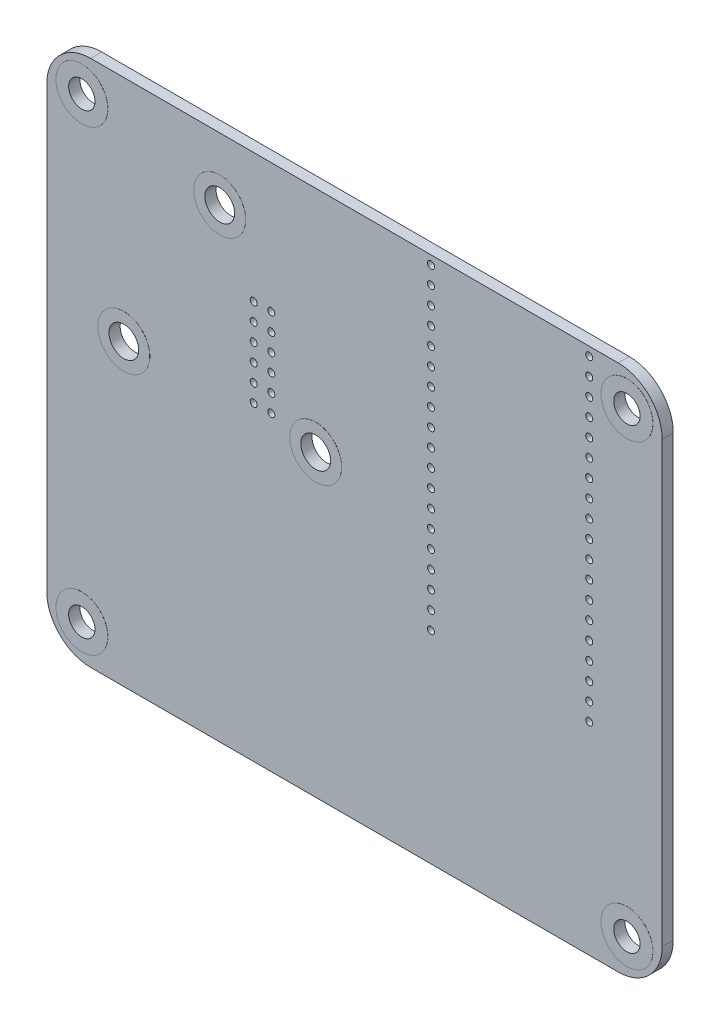
SolidWorks part; units mm, degrees
ref_plane "Front Plane" through (0, 0, 0) normal (0, 0, 1) x (1, 0, 0)
ref_plane "Top Plane" through (0, 0, 0) normal (0, 1, 0) x (1, 0, 0)
ref_plane "Right Plane" through (0, 0, 0) normal (1, 0, 0) x (0, 0, -1)
sketch "Sketch1" plane through (0, 0, 0) normal (0, 0, 1) x (1, 0, 0)
  line L1 (0, -76.2) -> (88.9, -76.2)
  line L2 (0, -76.2) -> (0, 0)
  line L3 (0, 0) -> (88.9, 0)
  line L4 (88.9, -76.2) -> (88.9, 0)
  point P4 (0, 0)
  point P5 (0, 0)
  dimension "D1" = 76.2
  dimension "D2" = 88.9
extrude "Boss-Extrude1" add sketch "Sketch1" along normal blind 1.6
sketch "Sketch2" plane through (0, 0, 0) normal (0, 0, -1) x (-1, 0, 0)
  circle A8 centre (-38.8564, -33) radius 2.15 construction
  circle A9 centre (-11.1436, -33) radius 2.15 construction
  circle A10 centre (-25, -9) radius 2.15 construction
  circle A11 centre (-38.8564, -33) radius 2.15
  circle A12 centre (-11.1436, -33) radius 2.15
  circle A13 centre (-25, -9) radius 2.15
extrude "Cut-Extrude1" cut sketch "Sketch2" against normal through all
sketch "Sketch4" plane through (0, 0, 0) normal (0, 0, -1) x (-1, 0, 0)
  line L0 (-44.45, 0) -> (-44.45, -76.2) construction
  line L1 (-88.9, 0) -> (0, 0) construction
  line L2 (0, -76.2) -> (-88.9, -76.2) construction
  line L3 (-88.9, -38.1) -> (0, -38.1) construction
  line L4 (-88.9, -76.2) -> (-88.9, 0) construction
  line L5 (0, 0) -> (0, -76.2) construction
  circle A0 centre (-5.08, -5.08) radius 1.905
  circle A1 centre (-83.82, -5.08) radius 1.905
  circle A2 centre (-83.82, -71.12) radius 1.905
  circle A3 centre (-5.08, -71.12) radius 1.905
  dimension "D1" = 3.81
  dimension "D2" = 5.08
  dimension "D3" = 5.08
extrude "Cut-Extrude2" cut sketch "Sketch4" against normal through all
fillet "Fillet1" radius 6.35 4 edges at (88.9, 0, 0.8) (88.9, -76.2, 0.8) (0, -76.2, 0.8) (0, 0, 0.8)
ref_plane "Plane1" through (44.45, 0, 0) normal (-1, 0, 0) x (0, 0, 1)
sketch "Sketch6" plane through (0, 0, 0) normal (0, 0, -1) x (-1, 0, 0)
  circle A0 centre (-5.08, -71.12) radius 3.75
  circle A1 centre (-5.08, -5.08) radius 3.75
  circle A2 centre (-11.1436, -33) radius 3.75
  circle A3 centre (-38.8564, -33) radius 3.75
  circle A4 centre (-25, -9) radius 3.75
  circle A5 centre (-83.82, -5.08) radius 3.75
  circle A6 centre (-83.82, -71.12) radius 3.75
  point P20 (-5.08, -71.12)
  circle M3 centre (-5.08, -71.12) radius 1.905
  circle M4 centre (-83.82, -71.12) radius 1.905
  circle M5 centre (-83.82, -5.08) radius 1.905
  circle M6 centre (-5.08, -5.08) radius 1.905
  circle M7 centre (-38.8564, -33) radius 2.15
  circle M8 centre (-11.1436, -33) radius 2.15
  circle M9 centre (-25, -9) radius 2.15
  dimension "D1" = 7.5
extrude "Boss-Extrude2" add sketch "Sketch6" along normal blind 0.01 contours A1 M6 | A4 M9 | A2 M8 | A0 M3 | A3 M7 | A5 M5 | A6 M4 region at (8.7239, -71.12, 0) region at (8.7239, -5.08, 0) region at (14.7875, -33, 0) region at (42.5003, -33, 0) region at (28.6439, -9, 0) region at (87.4639, -5.08, 0) region at (87.4639, -71.12, 0)
ref_plane "Plane2" through (0, 0, 0.8) normal (0, 0, 1) x (1, 0, 0)
mirror "Mirror1" about plane through (0, 0, 0.8) normal (0, 0, 1) of "Boss-Extrude2"
sketch "Sketch7" plane through (0, 0, 1.6) normal (0, 0, 1) x (1, 0, 0)
  line L4 (78.5658, -1.0536) -> (78.1658, -1.0536)
  line L5 (78.5658, -1.4536) -> (78.5658, -1.0536)
  line L6 (78.1658, -1.4536) -> (78.5658, -1.4536)
  line L7 (78.1658, -1.0536) -> (78.1658, -1.4536)
  line L8 (78.5658, -1.0536) -> (78.1658, -1.0536)
  line L11 (78.1658, -1.0536) -> (78.1658, -1.4536)
  circle A0 centre (29.897, -31.35) radius 0.508
  circle A1 centre (32.437, -31.35) radius 0.508
  circle A2 centre (32.437, -28.81) radius 0.508
  circle A3 centre (32.437, -26.27) radius 0.508
  circle A4 centre (32.437, -23.73) radius 0.508
  circle A5 centre (32.437, -21.19) radius 0.508
  circle A6 centre (32.437, -18.65) radius 0.508
  circle A7 centre (29.897, -28.81) radius 0.508
  circle A8 centre (29.897, -26.27) radius 0.508
  circle A9 centre (29.897, -23.73) radius 0.508
  circle A10 centre (29.897, -21.19) radius 0.508
  circle A11 centre (29.897, -18.65) radius 0.508
  circle A12 centre (78.3658, -1.2536) radius 0.508
  circle A13 centre (55.5058, -1.2536) radius 0.508
  circle A14 centre (55.5058, -3.7936) radius 0.508
  circle A15 centre (55.5058, -6.3336) radius 0.508
  circle A16 centre (55.5058, -8.8736) radius 0.508
  circle A17 centre (55.5058, -11.4136) radius 0.508
  circle A18 centre (55.5058, -13.9536) radius 0.508
  circle A19 centre (55.5058, -16.4936) radius 0.508
  circle A20 centre (55.5058, -19.0336) radius 0.508
  circle A21 centre (55.5058, -21.5736) radius 0.508
  circle A22 centre (55.5058, -24.1136) radius 0.508
  circle A23 centre (55.5058, -26.6536) radius 0.508
  circle A24 centre (55.5058, -29.1936) radius 0.508
  circle A25 centre (55.5058, -31.7336) radius 0.508
  circle A26 centre (55.5058, -34.2736) radius 0.508
  circle A27 centre (55.5058, -36.8136) radius 0.508
  circle A28 centre (55.5058, -39.3536) radius 0.508
  circle A29 centre (55.5058, -41.8936) radius 0.508
  circle A30 centre (55.5058, -44.4336) radius 0.508
  circle A31 centre (55.5058, -46.9736) radius 0.508
  circle A32 centre (78.3658, -3.7936) radius 0.508
  circle A33 centre (78.3658, -6.3336) radius 0.508
  circle A34 centre (78.3658, -8.8736) radius 0.508
  circle A35 centre (78.3658, -11.4136) radius 0.508
  circle A36 centre (78.3658, -13.9536) radius 0.508
  circle A37 centre (78.3658, -16.4936) radius 0.508
  circle A38 centre (78.3658, -19.0336) radius 0.508
  circle A39 centre (78.3658, -21.5736) radius 0.508
  circle A40 centre (78.3658, -24.1136) radius 0.508
  circle A41 centre (78.3658, -26.6536) radius 0.508
  circle A42 centre (78.3658, -29.1936) radius 0.508
  circle A43 centre (78.3658, -31.7336) radius 0.508
  circle A44 centre (78.3658, -34.2736) radius 0.508
  circle A45 centre (78.3658, -36.8136) radius 0.508
  circle A46 centre (78.3658, -39.3536) radius 0.508
  circle A47 centre (78.3658, -41.8936) radius 0.508
  circle A48 centre (78.3658, -44.4336) radius 0.508
  circle A49 centre (78.3658, -46.9736) radius 0.508
  point P0 (29.897, -31.35)
  point P6 (78.3658, -1.2536)
  point P30 (78.1658, -1.2536)
  point P32 (78.3658, -1.0536)
  dimension "D1" = 6
  dimension "D4" = 19
  dimension "D3" = 0
  dimension "D2" = 2
extrude "Cut-Extrude3" cut sketch "Sketch7" against normal through all contours A0 | A1 | A2 | A7 | A3 | A8 | A4 | A9 | A11 | A6 | A10 | A5 | A31 | A30 | A29 | A28 | A27 | A26 | A25 | A24 | A23 | A22 | A21 | A20 | A19 | A18 | A17 | A16 | A15 | A14 | A13 | A34 | A35 | A36 | A37 | A38 | A39 | A40 | A41 | A42 | A43 | A12 | A32 | A33 | A44 | A45 | A46 | A47 | A48 | A49 region at (29.897, -31.35, 1.6) region at (32.437, -31.35, 1.6) region at (32.437, -28.81, 1.6) region at (32.437, -26.27, 1.6) region at (32.437, -23.73, 1.6) region at (32.437, -21.19, 1.6) region at (32.437, -18.65, 1.6) region at (29.897, -28.81, 1.6) region at (29.897, -26.27, 1.6) region at (29.897, -23.73, 1.6) region at (29.897, -21.19, 1.6) region at (29.897, -18.65, 1.6) region at (55.5058, -34.2736, 1.6) region at (55.5058, -36.8136, 1.6) region at (55.5058, -39.3536, 1.6) region at (55.5058, -41.8936, 1.6) region at (55.5058, -44.4336, 1.6) region at (55.5058, -46.9736, 1.6)
sketch "Sketch5" plane through (0, 0, 1.6) normal (0, 0, 1) x (1, 0, 0)
  line L0 (0, -6.35) -> (0, -69.85) construction
  line L1 (6.35, -76.2) -> (82.55, -76.2) construction
  line L2 (82.55, 0) -> (6.35, 0) construction
  line L3 (0, -6.35) -> (0, -69.85) construction
  line L4 (82.55, 0) -> (6.35, 0) construction
  circle A0 centre (5.08, -71.12) radius 1.905 construction
  circle A3 centre (5.08, -71.12) radius 1.905
  circle A5 centre (11.1436, -33) radius 2.15 construction
  circle A7 centre (15.8595, 55.8131) radius 3 construction
  circle A10 centre (38.8564, -33) radius 2.15 construction
  point P0 (5.08, -5.08)
  point P1 (5.08, -71.12)
  point P3 (83.82, -71.12)
  point P5 (83.82, -5.08)
  point P7 (25, -9)
  point P9 (32.437, -18.65)
  point P15 (0, -76.2)
  point P17 (38.8564, -33)
  point P26 (0, 0)
  point P27 (0, 0)
  point P30 (0, 0)
  point P31 (78.3658, -1.2536)
  point P32 (11.1436, -33)
  point P40 (0, 0)
  point P41 (0, 0)
  dimension "D9" = 33
  dimension "D10" = 3.81
  dimension "D2" = 5.08
  dimension "D3" = 9
  dimension "D4" = 25
  dimension "D5" = 71.12
  dimension "D6" = 11.1436
  dimension "D7" = 38.8564
  dimension "D8" = 83.82
  dimension "D12" = 32.437
  dimension "D13" = 78.3658
  dimension "D14" = 55.8131
  dimension "D15" = 18.65
  dimension "D16" = 18.65
  dimension "D11" = 5.08
